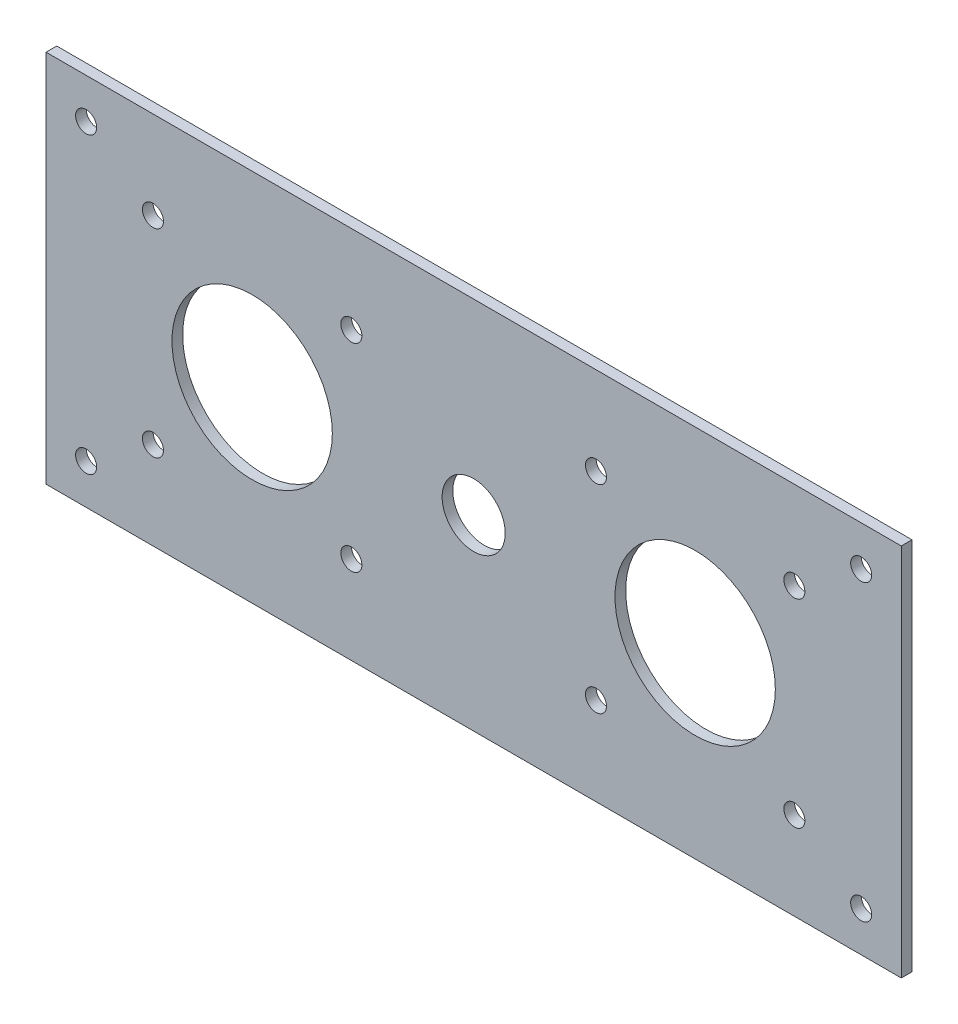
SolidWorks part; units mm, degrees
ref_plane "Front Plane" through (0, 0, 0) normal (0, 0, 1) x (1, 0, 0)
ref_plane "Top Plane" through (0, 0, 0) normal (0, 1, 0) x (1, 0, 0)
ref_plane "Right Plane" through (0, 0, 0) normal (1, 0, 0) x (0, 0, -1)
sketch "Sketch2" plane through (0, 0, 0) normal (0, 0, 1) x (1, 0, 0)
  line L0 (-29.06, 23.57) -> (-76.2, 23.57) construction
  line L1 (-101.6, -44.45) -> (101.6, -44.45)
  line L2 (-101.6, -44.45) -> (-101.6, 44.45)
  line L3 (-101.6, 44.45) -> (101.6, 44.45)
  line L4 (101.6, -44.45) -> (101.6, 44.45)
  line L5 (-101.6, -44.45) -> (101.6, 44.45) construction
  line L6 (-101.6, 44.45) -> (101.6, -44.45) construction
  line L7 (-76.2, 23.57) -> (-76.2, -23.57) construction
  line L8 (-76.2, -23.57) -> (-29.06, -23.57) construction
  line L9 (-29.06, -23.57) -> (-29.06, 23.57) construction
  line L10 (-76.2, 0) -> (-101.6, 0) construction
  line L11 (-52.63, 0) -> (-52.63, 23.57) construction
  line L12 (29.06, -23.57) -> (76.2, -23.57) construction
  line L13 (76.2, -23.57) -> (76.2, 23.57) construction
  line L14 (76.2, 23.57) -> (29.06, 23.57) construction
  line L15 (29.06, 23.57) -> (29.06, -23.57) construction
  line L16 (-52.63, 0) -> (-29.06, 0) construction
  line L17 (76.2, 0) -> (101.6, 0) construction
  line L18 (52.63, 0) -> (29.06, 0) construction
  line L19 (52.63, 0) -> (52.63, 23.57) construction
  circle A0 centre (-76.2, -23.57) radius 2.5
  circle A1 centre (-29.06, -23.57) radius 2.5
  circle A2 centre (-29.06, 23.57) radius 2.5
  circle A3 centre (-76.2, 23.57) radius 2.5
  circle A4 centre (29.06, 23.57) radius 2.5
  circle A5 centre (76.2, 23.57) radius 2.5
  circle A7 centre (29.06, -23.57) radius 2.5
  circle A8 centre (76.2, -23.57) radius 2.5
  circle A9 centre (-52.63, 0) radius 19.05
  circle A10 centre (52.63, 0) radius 19.05
  point P0 (0, 0)
  point P17 (101.6, 0)
  point P23 (-101.6, 0)
  dimension "D3" = 5
  dimension "D6" = 38.1
  dimension "D1" = 47.14
  dimension "D2" = 88.9
  dimension "D4" = 203.2
  dimension "D5" = 25.4
extrude "Boss-Extrude1" add sketch "Sketch2" along normal mid plane 2.54
sketch "Sketch3" plane through (0, 0, 1.27) normal (0, 0, 1) x (1, 0, 0)
  line L0 (-101.6, 34.925) -> (-92.075, 34.925) construction
  line L1 (-101.6, 44.45) -> (-101.6, -44.45) construction
  line L2 (-92.075, 34.925) -> (-92.075, 44.45) construction
  line L3 (101.6, 44.45) -> (-101.6, 44.45) construction
  line L4 (92.075, 44.45) -> (92.075, 34.925) construction
  line L5 (92.075, 34.925) -> (101.6, 34.925) construction
  line L6 (101.6, -44.45) -> (101.6, 44.45) construction
  line L7 (92.075, -44.45) -> (92.075, -34.925) construction
  line L8 (-101.6, -44.45) -> (101.6, -44.45) construction
  line L9 (92.075, -34.925) -> (101.6, -34.925) construction
  line L10 (-92.075, -44.45) -> (-92.075, -34.925) construction
  line L11 (-92.075, -34.925) -> (-101.6, -34.925) construction
  circle A0 centre (-92.075, 34.925) radius 2.5
  circle A1 centre (-92.075, -34.925) radius 2.5
  circle A2 centre (92.075, -34.925) radius 2.5
  circle A3 centre (92.075, 34.925) radius 2.5
  dimension "D2" = 5
  dimension "D1" = 9.525
extrude "Cut-Extrude1" cut sketch "Sketch3" against normal through all
sketch "Sketch4" plane through (0, 0, 1.27) normal (0, 0, 1) x (1, 0, 0)
  circle A0 centre (0, 0) radius 7.5
  dimension "D1" = 15
extrude "Cut-Extrude2" cut sketch "Sketch4" against normal through all both and the other way through all
sketch "Sketch5" plane through (0, 0, 1.27) normal (0, 0, 1) x (1, 0, 0)
  line L0 (-81.2, 23.57) -> (-71.2, 23.57) construction
  line L1 (-81.2, 26.07) -> (-71.2, 26.07)
  line L2 (-81.2, 21.07) -> (-71.2, 21.07)
  line L3 (-34.06, 23.57) -> (-24.06, 23.57) construction
  line L4 (-34.06, 26.07) -> (-24.06, 26.07)
  line L5 (-34.06, 21.07) -> (-24.06, 21.07)
  line L6 (-34.06, -23.57) -> (-24.06, -23.57) construction
  line L7 (-34.06, -21.07) -> (-24.06, -21.07)
  line L8 (-34.06, -26.07) -> (-24.06, -26.07)
  line L9 (-71.2, -23.57) -> (-81.2, -23.57) construction
  line L10 (-71.2, -26.07) -> (-81.2, -26.07)
  line L11 (-71.2, -21.07) -> (-81.2, -21.07)
  line L12 (24.06, -23.57) -> (34.06, -23.57) construction
  line L13 (24.06, -21.07) -> (34.06, -21.07)
  line L14 (24.06, -26.07) -> (34.06, -26.07)
  line L15 (71.2, -23.57) -> (81.2, -23.57) construction
  line L16 (71.2, -21.07) -> (81.2, -21.07)
  line L17 (71.2, -26.07) -> (81.2, -26.07)
  line L18 (71.2, 23.57) -> (81.2, 23.57) construction
  line L19 (71.2, 26.07) -> (81.2, 26.07)
  line L20 (71.2, 21.07) -> (81.2, 21.07)
  line L21 (24.06, 23.57) -> (34.06, 23.57) construction
  line L22 (24.06, 26.07) -> (34.06, 26.07)
  line L23 (24.06, 21.07) -> (34.06, 21.07)
  arc A0 (-81.2, 26.07) -> (-81.2, 21.07) centre (-81.2, 23.57) ccw
  arc A1 (-71.2, 21.07) -> (-71.2, 26.07) centre (-71.2, 23.57) ccw
  arc A2 (-34.06, 26.07) -> (-34.06, 21.07) centre (-34.06, 23.57) ccw
  arc A3 (-24.06, 21.07) -> (-24.06, 26.07) centre (-24.06, 23.57) ccw
  arc A4 (-34.06, -21.07) -> (-34.06, -26.07) centre (-34.06, -23.57) ccw
  arc A5 (-24.06, -26.07) -> (-24.06, -21.07) centre (-24.06, -23.57) ccw
  arc A6 (-71.2, -26.07) -> (-71.2, -21.07) centre (-71.2, -23.57) ccw
  arc A7 (-81.2, -21.07) -> (-81.2, -26.07) centre (-81.2, -23.57) ccw
  arc A8 (24.06, -21.07) -> (24.06, -26.07) centre (24.06, -23.57) ccw
  arc A9 (34.06, -26.07) -> (34.06, -21.07) centre (34.06, -23.57) ccw
  arc A10 (71.2, -21.07) -> (71.2, -26.07) centre (71.2, -23.57) ccw
  arc A11 (81.2, -26.07) -> (81.2, -21.07) centre (81.2, -23.57) ccw
  arc A12 (71.2, 26.07) -> (71.2, 21.07) centre (71.2, 23.57) ccw
  arc A13 (81.2, 21.07) -> (81.2, 26.07) centre (81.2, 23.57) ccw
  arc A14 (24.06, 26.07) -> (24.06, 21.07) centre (24.06, 23.57) ccw
  arc A15 (34.06, 21.07) -> (34.06, 26.07) centre (34.06, 23.57) ccw
  point P2 (-76.2, 23.57)
  point P9 (-29.06, 23.57)
  point P17 (-29.06, -23.57)
  point P25 (-76.2, -23.57)
  point P33 (29.06, -23.57)
  point P41 (76.2, -23.57)
  point P49 (76.2, 23.57)
  point P57 (29.06, 23.57)
  dimension "D6" = 5
  dimension "D1" = 5
  dimension "D2" = 10
  dimension "D3" = 5
  dimension "D4" = 5
  dimension "D5" = 5
  dimension "5" = 5
  dimension "D7" = 5
  dimension "D8" = 5
extrude "Slots Cut-Extrude" [suppressed] cut sketch "Sketch5" against normal through all both and the other way through all
